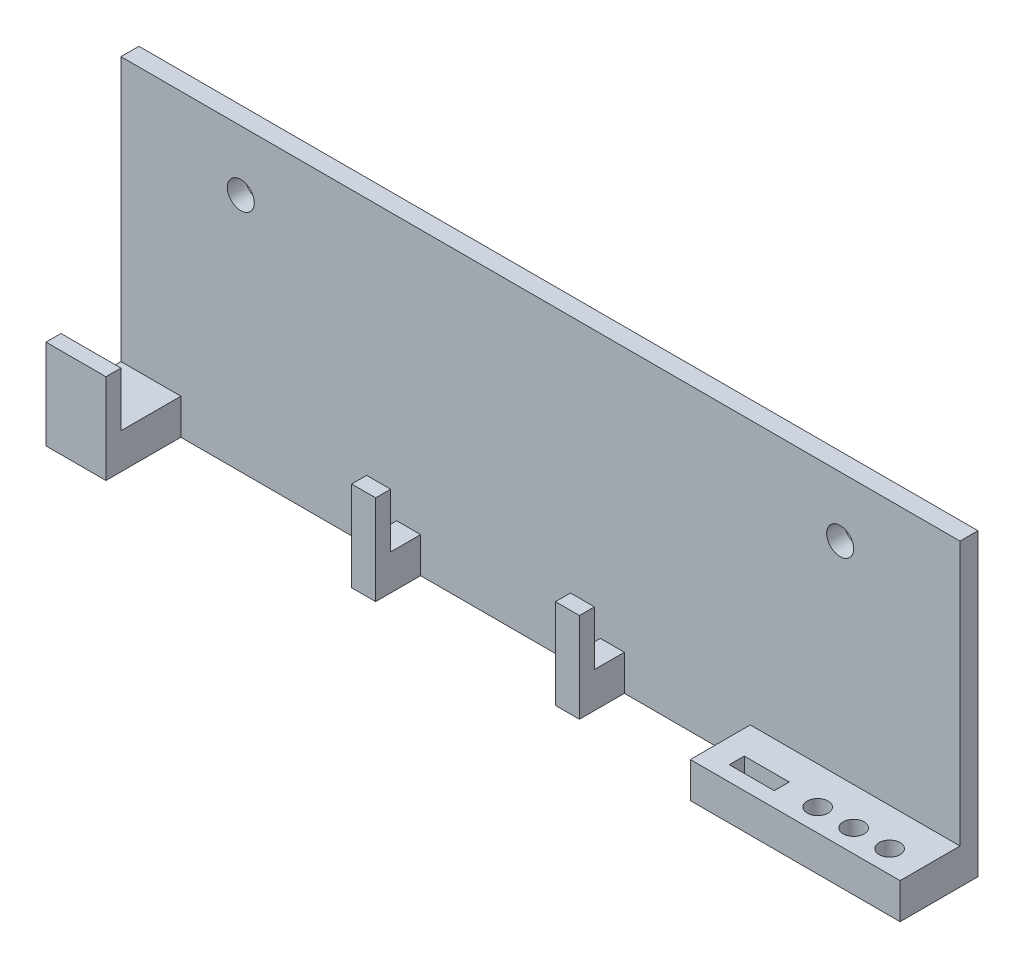
SolidWorks part; units mm, degrees
ref_plane "Front Plane" through (0, 0, 0) normal (0, 0, 1) x (1, 0, 0)
ref_plane "Top Plane" through (0, 0, 0) normal (0, 1, 0) x (1, 0, 0)
ref_plane "Right Plane" through (0, 0, 0) normal (1, 0, 0) x (0, 0, -1)
sketch "Sketch1" plane through (0, 0, 0) normal (1, 0, 0) x (0, 0, -1)
  line L7 (0, -33) -> (3, -33)
  line L8 (3, 17) -> (3, -33)
  line L9 (3, 17) -> (0, 17)
  line L10 (0, 17) -> (0, -33)
  dimension "D4" = 3
  dimension "D5" = 50
extrude "Boss-Extrude1" add sketch "Sketch1" along normal blind 140 contours L9 | L8 L9 L7 region at (0, -8, -1.5)
sketch "Sketch3" plane through (0, 0, 0) normal (0, 0, 1) x (1, 0, 0)
  line L1 (0, -33) -> (10, -33)
  line L2 (0, -33) -> (0, -27.0594)
  line L3 (0, -27.0594) -> (10, -27.0594)
  line L4 (10, -33) -> (10, -27.0594)
  line L5 (50, -33) -> (46, -33)
  line L6 (50, -33) -> (50, -27.0594)
  line L7 (50, -27.0594) -> (46, -27.0594)
  line L8 (46, -33) -> (46, -27.0594)
  line L10 (80, -33) -> (84, -33)
  line L11 (80, -33) -> (80, -27.0594)
  line L12 (80, -27.0594) -> (84, -27.0594)
  line L13 (84, -33) -> (84, -27.0594)
  line L14 (105, -33) -> (140, -33)
  line L15 (105, -33) -> (105, -27.0594)
  line L16 (105, -27.0594) -> (140, -27.0594)
  line L17 (140, -33) -> (140, -27.0594)
  point P11 (10, -30.0297)
  dimension "D1" = 10
  dimension "D2" = 40
  dimension "D3" = 4
  dimension "D4" = 30
  dimension "D5" = 4
  dimension "D6" = 25
extrude "Boss-Extrude2" add sketch "Sketch3" along normal blind 10
sketch "Sketch5" plane through (0, -33, 0) normal (0, -1, 0) x (1, 0, 0)
  line L0 (84, 10) -> (84, 0) construction
  line L1 (46, 10) -> (84, 10)
  line L2 (46, 10) -> (46, 5)
  line L3 (46, 5) -> (84, 5)
  line L4 (84, 10) -> (84, 5)
extrude "Cut-Extrude2" cut sketch "Sketch5" against normal blind 15
sketch "Sketch6" plane through (0, -33, 0) normal (0, -1, 0) x (1, 0, 0)
  line L0 (10, 10) -> (10, 0) construction
  line L1 (0, 10) -> (10, 10)
  line L2 (0, 10) -> (0, 12.5)
  line L3 (0, 12.5) -> (10, 12.5)
  line L4 (10, 10) -> (10, 12.5)
  line L5 (46, 5) -> (50, 5)
  line L6 (46, 5) -> (46, 7.5)
  line L7 (46, 7.5) -> (50, 7.5)
  line L8 (50, 5) -> (50, 7.5)
  line L9 (80, 5) -> (84, 5)
  line L10 (80, 5) -> (80, 7.5)
  line L11 (80, 7.5) -> (84, 7.5)
  line L12 (84, 5) -> (84, 7.5)
  line L13 (50, 5) -> (50, 0) construction
  line L14 (84, 5) -> (84, 0) construction
  dimension "D1" = 2.5
extrude "Boss-Extrude4" add sketch "Sketch6" against normal blind 15
sketch "Sketch7" plane through (0, -27.0594, 0) normal (0, 1, 0) x (1, 0, 0)
  line L0 (140, -10) -> (105, -10) construction
  line L1 (109, -5) -> (116.5, -5)
  line L2 (109, -5) -> (109, -7.5)
  line L3 (109, -7.5) -> (116.5, -7.5)
  line L4 (116.5, -5) -> (116.5, -7.5)
  line L5 (105, -10) -> (105, 0) construction
  circle A0 centre (128.5, -6.25) radius 1.75
  circle A1 centre (122.5, -6.25) radius 1.75
  circle A2 centre (134.5, -6.25) radius 1.75
  point P13 (116.5, -6.25)
  dimension "D1" = 3.5
  dimension "D7" = 6
  dimension "D8" = 3.5
  dimension "D9" = 6
  dimension "D2" = 2.5
  dimension "D3" = 4
  dimension "D4" = 7.5
  dimension "D5" = 2.5
  dimension "D6" = 6
extrude "Cut-Extrude3" cut sketch "Sketch7" against normal blind 15
sketch "Sketch8" plane through (0, 0, 0) normal (0, 0, 1) x (1, 0, 0)
  line L0 (0, 17) -> (0, -27.0594) construction
  line L1 (140, 17) -> (140, -27.0594) construction
  line L2 (140, 17) -> (0, 17) construction
  circle A0 centre (20, 7) radius 2.25
  circle A1 centre (120, 7) radius 2.25
  dimension "D1" = 20
  dimension "D2" = 20
  dimension "D3" = 10
  dimension "D4" = 10
  dimension "D5" = 4.5
  dimension "D6" = 4.5
extrude "Cut-Extrude4" cut sketch "Sketch8" against normal blind 15
